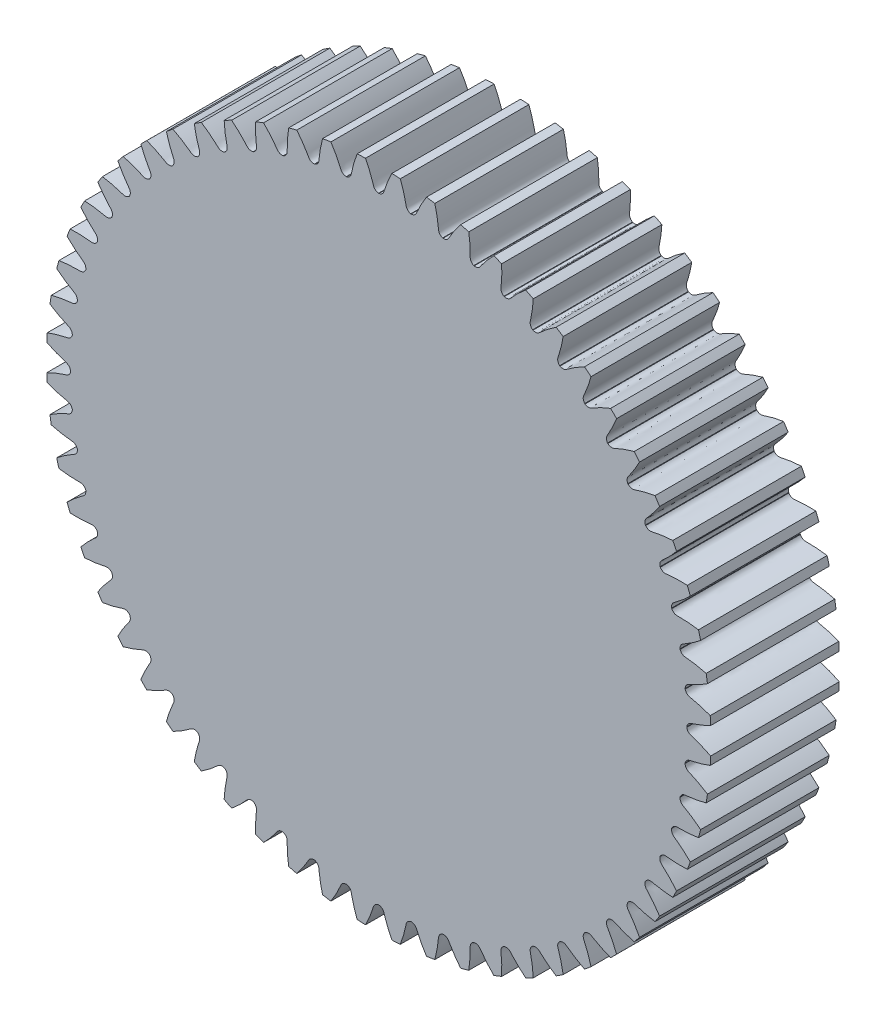
SolidWorks part; units mm, degrees
ref_plane "前视基准面" through (0, 0, 0) normal (0, 0, 1) x (1, 0, 0)
ref_plane "上视基准面" through (0, 0, 0) normal (0, 1, 0) x (1, 0, 0)
ref_plane "右视基准面" through (0, 0, 0) normal (1, 0, 0) x (0, 0, -1)
other "Configuration Table"
sketch "草图1" plane through (0, 0, 0) normal (0, 0, 1) x (1, 0, 0)
  circle A0 centre (0, 0) radius 15.5
extrude "凸台-拉伸1" add sketch "草图1" along normal blind 6
ref_axis "基准轴1" through (0, 0, -0.3) along (0, 0, 1)
sketch "草图2" plane through (0, 0, 0) normal (0, 0, 1) x (1, 0, 0)
  line L0 (0, 0) -> (0, 15.5) construction
  circle A0 centre (0, 0) radius 15.5 construction
  arc A1 (0.01, 14.375) -> (-0.01, 14.375) centre (0, 0) ccw
  arc A2 (2.1043, 17.5326) -> (-2.1043, 17.5326) centre (0, 0) ccw
  spline S0 degree 3 poles (0.01, 14.375) (0.2152, 14.4122) (0.2483, 14.5839) (0.3119, 14.7751) (0.342, 14.8616) (0.3759, 14.9526) (0.4137, 15.0482) (0.4555, 15.1483) (0.5016, 15.2526) (0.5522, 15.3611) (0.6074, 15.4736) (0.6675, 15.5901) (0.7325, 15.7102) (0.8027, 15.834) (0.8783, 15.9611) (0.9593, 16.0915) (1.046, 16.225) (1.1385, 16.3614) (1.237, 16.5005) (1.3416, 16.6422) (1.4525, 16.7862) (1.5697, 16.9323) (1.6935, 17.0805) (1.8698, 17.2831) (2.0086, 17.4331) (2.1043, 17.5326) knots 0 0 0 0 0.111713 0.134139 0.158036 0.183407 0.210249 0.238564 0.268351 0.299611 0.332343 0.366547 0.402223 0.439372 0.477993 0.518087 0.559653 0.602691 0.647201 0.693184 0.740639 0.789567 0.839967 0.891839 1 1 1 1
  spline S1 degree 3 poles (-0.01, 14.375) (-0.2152, 14.4122) (-0.2483, 14.5839) (-0.3119, 14.7751) (-0.342, 14.8616) (-0.3759, 14.9526) (-0.4137, 15.0482) (-0.4555, 15.1483) (-0.5016, 15.2526) (-0.5522, 15.3611) (-0.6074, 15.4736) (-0.6675, 15.5901) (-0.7325, 15.7102) (-0.8027, 15.834) (-0.8783, 15.9611) (-0.9593, 16.0915) (-1.046, 16.225) (-1.1385, 16.3614) (-1.237, 16.5005) (-1.3416, 16.6422) (-1.4525, 16.7862) (-1.5697, 16.9323) (-1.6935, 17.0805) (-1.8698, 17.2831) (-2.0086, 17.4331) (-2.1043, 17.5326) knots 0 0 0 0 0.111713 0.134139 0.158036 0.183407 0.210249 0.238564 0.268351 0.299611 0.332343 0.366547 0.402223 0.439372 0.477993 0.518087 0.559653 0.602691 0.647201 0.693184 0.740639 0.789567 0.839967 0.891839 1 1 1 1
extrude "切除-拉伸1" cut sketch "草图2" along normal through all
pattern_circular "阵列(圆周)1" count 60 every 6 about axis through (0, 0, -0.3) along (0, 0, 1) of "切除-拉伸1"
sketch "草图3" plane through (0, 0, 0) normal (0, 0, 1) x (1, 0, 0)
  circle A0 centre (0, 0) radius 15 construction
  dimension "Dn" = 30
